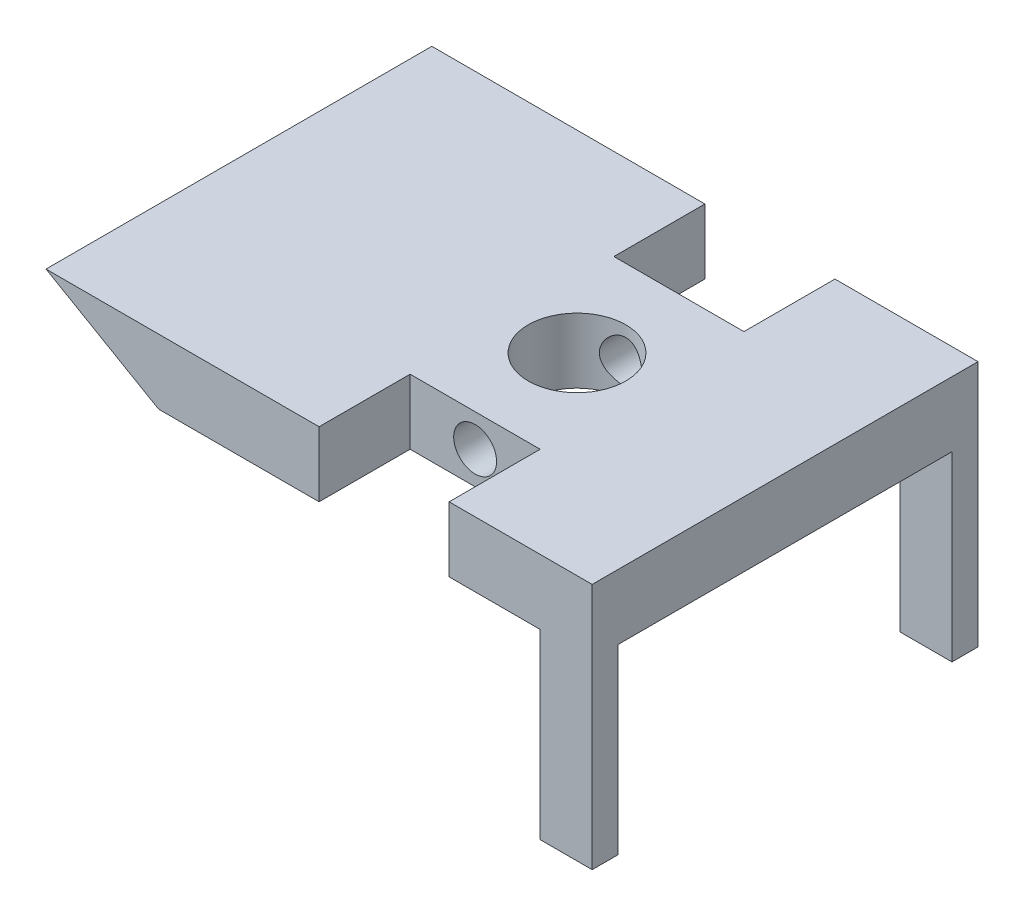
SolidWorks part; units mm, degrees
ref_plane "Front Plane" through (0, 0, 0) normal (0, 0, 1) x (1, 0, 0)
ref_plane "Top Plane" through (0, 0, 0) normal (0, 1, 0) x (1, 0, 0)
ref_plane "Right Plane" through (0, 0, 0) normal (1, 0, 0) x (0, 0, -1)
sketch "Sketch3" plane through (0, 0, 0) normal (0, 0, 1) x (1, 0, 0)
  line L0 (-21, 2.5) -> (-12.3397, -2.5)
  line L1 (-12.3397, -2.5) -> (21, -2.5)
  line L3 (-21, 2.5) -> (21, 2.5)
  line L4 (21, -2.5) -> (21, 2.5)
  line L5 (-13.8202, -1.6453) -> (21, 2.5) construction
  line L6 (-21, 2.5) -> (21, -2.5) construction
  arc A0 (-21, 2.5) -> (-12.3397, -2.5) centre (-22.4997, -10.0976) cw construction
  point P0 (0, 0)
  point P6 (0, 2.5)
  dimension "D1" = 42
  dimension "D2" = 150
  dimension "D4" = 5
extrude "Boss-Extrude1" add sketch "Sketch3" along normal mid plane 29.67
sketch "Sketch4" plane through (0, 0, 14.835) normal (0, 0, 1) x (1, 0, 0)
  line L0 (21, -2.5) -> (21, 2.5) construction
  line L1 (21, 2.5) -> (-21, 2.5) construction
  line L2 (10, -2.5) -> (0, -2.5)
  line L3 (10, -2.5) -> (10, 2.5)
  line L4 (10, 2.5) -> (0, 2.5)
  line L5 (0, -2.5) -> (0, 2.5)
  line L6 (10, -2.5) -> (0, 2.5) construction
  line L7 (10, 2.5) -> (0, -2.5) construction
  circle A2 centre (5, 0) radius 1.65
  dimension "D1" = 3.3
  dimension "D2" = 5
  dimension "D5" = 16
extrude "Cut-Extrude1" cut sketch "Sketch4" against normal up to next contours A2 region at (5, 0, 14.835)
extrude "Cut-Extrude3" cut sketch "Sketch4<3>" against normal blind 7
sketch "Sketch4<3>" plane through (0, 0, 14.835) normal (0, 0, 1) x (1, 0, 0) same geometry as "Sketch4"
mirror "Mirror1" about plane through (0, 0, 0) normal (0, 0, 1) of "Cut-Extrude3"
sketch "Sketch5" plane through (0, 2.5, 0) normal (0, 1, 0) x (1, 0, 0)
  line L0 (21, -14.835) -> (21, 14.835) construction
  circle A0 centre (5, 0) radius 3.75
  point P7 (21, 0)
  dimension "D2" = 7.5
  dimension "D1" = 16
extrude "Cut-Extrude2" cut sketch "Sketch5" against normal up to next
sketch "Sketch6" plane through (0, 0, 14.835) normal (0, 0, 1) x (1, 0, 0)
  line L0 (21, -2.5) -> (21, -16.5)
  line L1 (21, -16.5) -> (17, -16.5)
  line L2 (17, -16.5) -> (17, -2.5)
  line L3 (-12.3397, -2.5) -> (0, -2.5) construction
  line L4 (17, -2.5) -> (21, -2.5)
  dimension "D1" = 14
  dimension "D2" = 4
extrude "Boss-Extrude2" add sketch "Sketch6" against normal up to surface (29.67 mm away) up to face at (-8.3349, 0, -14.835)
sketch "Sketch7" plane through (21, 0, 0) normal (1, 0, 0) x (0, 0, -1)
  line L0 (14.835, -16.5) -> (-14.835, -16.5) construction
  line L1 (-12.835, -16.5) -> (12.835, -16.5)
  line L2 (-12.835, -16.5) -> (-12.835, -2.5)
  line L3 (-12.835, -2.5) -> (12.835, -2.5)
  line L4 (12.835, -16.5) -> (12.835, -2.5)
  point P6 (0, -2.5)
  point P9 (0, 0)
  dimension "D1" = 2
extrude "Cut-Extrude4" cut sketch "Sketch7" against normal blind 10
